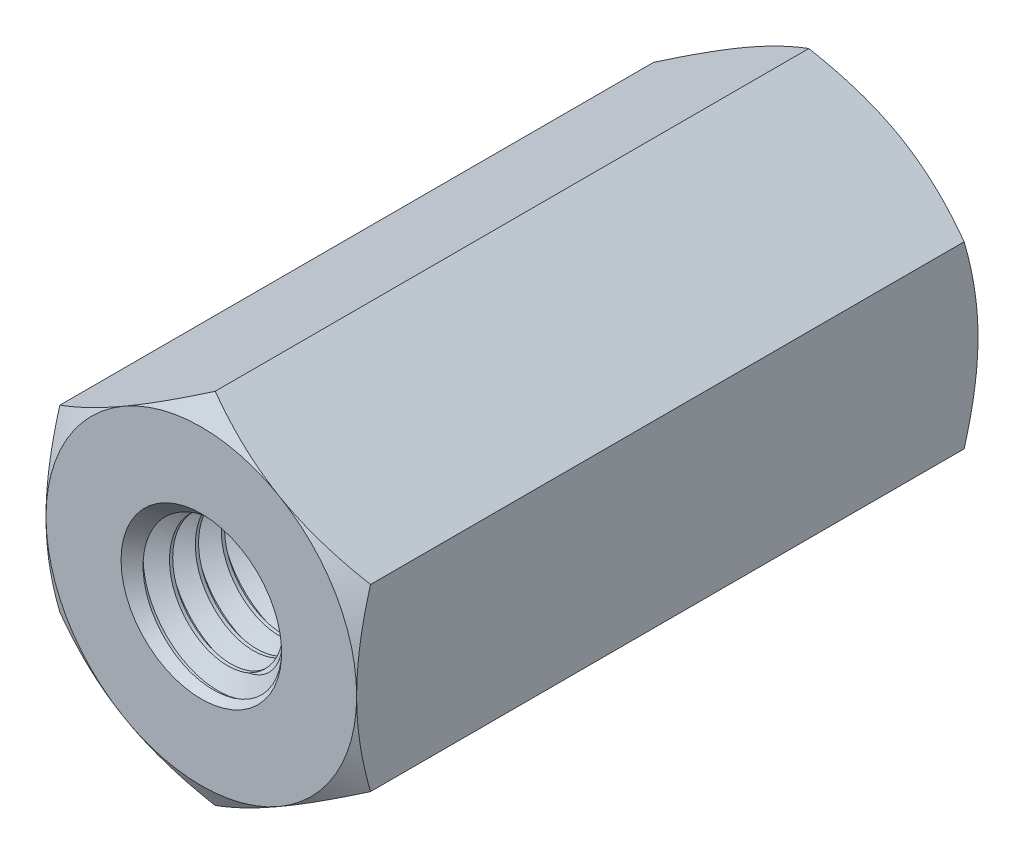
SolidWorks part; units mm, degrees
ref_plane "Front Plane" through (0, 0, 0) normal (0, 0, 1) x (1, 0, 0)
ref_plane "Top Plane" through (0, 0, 0) normal (0, 1, 0) x (1, 0, 0)
ref_plane "Right Plane" through (0, 0, 0) normal (1, 0, 0) x (0, 0, -1)
sketch "Sketch3" plane through (0, 0, 0) normal (1, 0, 0) x (0, 0, -1)
  line L0 (-6, 0) -> (6, 0) construction
  line L1 (0, 3) -> (0, -3) construction
  line L2 (-6, 1.5) -> (-6, -1.5) construction
  line L3 (-6, 3) -> (6, 3) construction
  point P2 (-3.525, 0)
  point P3 (3.525, 0)
  dimension "Length" = 12
  dimension "Min Thread Length" = 9.525
  dimension "D1" = 9.525
  dimension "Thread Dia" = 3
  dimension "Hex" = 6
  dimension "D2" = 12
sketch "Sketch1" plane through (0, 0, 0) normal (0, 0, 1) x (1, 0, 0)
  line L1 (0, 3.4641) -> (-3, 1.7321)
  line L2 (-3, 1.7321) -> (-3, -1.7321)
  line L3 (-3, -1.7321) -> (0, -3.4641)
  line L4 (0, -3.4641) -> (3, -1.7321)
  line L5 (3, -1.7321) -> (3, 1.7321)
  line L6 (3, 1.7321) -> (0, 3.4641)
  circle A0 centre (0, 0) radius 3 construction
  circle A1 centre (0, 0) radius 1.5
extrude "Extrude1" add sketch "Sketch1" along normal up to vertex (6 mm away) and the other way up to vertex (6 mm away) up to point (0, 0, 6) other way up to point (0, 0, -6)
sketch "Sketch11" plane through (0, 0, -6) normal (0, 0, -1) x (-1, 0, 0)
  circle A0 centre (0, 0) radius 1.5 construction
  circle A1 centre (0, 0) radius 1.5
curve "Helix/Spiral1" pitch 0.5 height 12.5 radius 1.5 centre (0, 0, -6) axis (0, 0, 1) start towards (0, 1, 0) parameters "Pitch"=0.5
sketch "Sketch12" plane through (0, 0, 0) normal (1, 0, 0) x (0, 0, -1)
  line L0 (6.4375, 1.5) -> (6, 1.5)
  line L1 (6.4375, 1.5) -> (6.25, 1.1752)
  line L2 (6.25, 1.1752) -> (6.1875, 1.1752)
  line L3 (6.1875, 1.1752) -> (6, 1.5)
  line L4 (6.2188, 1.1752) -> (6.2188, 1.5) construction
  line L5 (6.3438, 1.3376) -> (6.0938, 1.3376) construction
  dimension "D1" = 0.0625
  dimension "D2" = 0.25
  dimension "D3" = 60
sweep "Sweep1" add profiles "Sketch12" path "Helix/Spiral1"
sketch "Sketch6" plane through (0, 0, -6) normal (0, 0, -1) x (-1, 0, 0)
  line L6 (0, 3.4641) -> (-3, 1.7321)
  line L7 (-3, 1.7321) -> (-3, -1.7321)
  line L8 (-3, -1.7321) -> (0, -3.4641)
  line L9 (0, -3.4641) -> (3, -1.7321)
  line L10 (3, -1.7321) -> (3, 1.7321)
  line L11 (3, 1.7321) -> (0, 3.4641)
  line L12 (0, 3.4641) -> (-3, 1.7321)
  line L13 (-3, 1.7321) -> (-3, -1.7321)
  line L14 (-3, -1.7321) -> (0, -3.4641)
  line L15 (0, -3.4641) -> (3, -1.7321)
  line L16 (3, -1.7321) -> (3, 1.7321)
  line L17 (3, 1.7321) -> (0, 3.4641)
  dimension "D1" = 0
extrude "Extrude2" cut sketch "Sketch6" along normal through all
sketch "Sketch7" plane through (0, 0, -6) normal (0, 0, -1) x (-1, 0, 0)
  circle A2 centre (0, 0) radius 1.5508
  circle A3 centre (0, 0) radius 1.5508
  dimension "D1" = 0.0508
extrude "Extrude3" cut sketch "Sketch7" against normal through all draft 43
sketch "Sketch8" plane through (0, 0, -6) normal (0, 0, -1) x (-1, 0, 0)
  circle A0 centre (0, 0) radius 3 construction
  circle A1 centre (0, 0) radius 3
extrude "Extrude4" cut sketch "Sketch8" against normal through all draft 60 flip side to cut
mirror "Mirror1" about plane through (0, 0, 0) normal (0, 0, 1) of "Extrude2", "Extrude3", "Extrude4"
sketch "Sketch9" [suppressed] plane through (0, 0, 0) normal (1, 0, 0) x (0, 0, -1)
  line L1 (-19.7, 1.5508) -> (19.7, 1.5508)
  line L2 (-19.7, 1.5508) -> (-19.7, 0)
  line L3 (-19.7, 0) -> (19.7, 0)
  line L4 (19.7, 1.5508) -> (19.7, 0)
  line L7 (-26, 0) -> (26, 0) construction
revolve "Revolve" [suppressed] add sketch "Sketch9" angle 360 about L0
sketch "Sketch10" [suppressed] plane through (0, 0, 0) normal (1, 0, 0) x (0, 0, -1)
  line L0 (26, 1.5) -> (19.7, 1.5)
  line L1 (-26, 1.5) -> (-19.7, 1.5)
  line L2 (19.7, 1.5) -> (19.7, -1.5)
  line L3 (-26, -1.5508) -> (-19.7, -1.5508)
  line L4 (-19.7, 1.5) -> (-19.7, -1.5508)
  line L5 (19.7, -1.5) -> (26, -1.5)
equation "\"D1@Sketch3\" = \"Min Thread Length@Sketch3\""
equation "\"D3@Helix/Spiral1\" = \"Length@Sketch3\"+\"Pitch@Helix/Spiral1\""
equation "\"D1@Sketch12\" = \"Pitch@Helix/Spiral1\"*.125"
equation "\"D2@Sketch12\" = \"Pitch@Helix/Spiral1\"*.5"
equation "\"D2@Sketch3\" = \"Length@Sketch3\""
